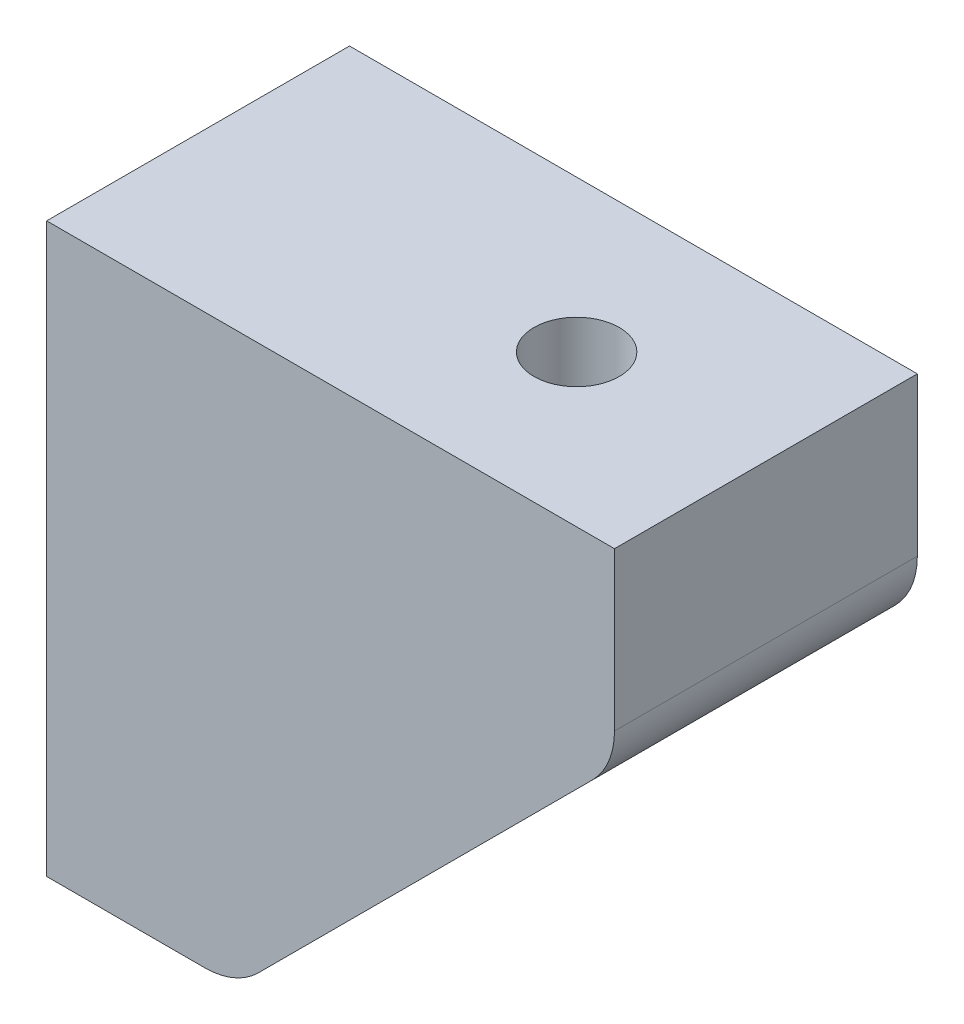
SolidWorks part; units mm, degrees
ref_plane "Front Plane" through (0, 0, 0) normal (0, 0, 1) x (1, 0, 0)
ref_plane "Top Plane" through (0, 0, 0) normal (0, 1, 0) x (1, 0, 0)
ref_plane "Right Plane" through (0, 0, 0) normal (1, 0, 0) x (0, 0, -1)
sketch "Sketch1" plane through (0, 0, 0) normal (0, 0, 1) x (1, 0, 0)
  line L0 (0, 0) -> (10, 0)
  line L1 (10, 0) -> (30, 20)
  line L2 (30, 20) -> (30, 30)
  line L3 (30, 30) -> (0, 30)
  line L4 (0, 30) -> (0, 0)
  line L5 (10, 0) -> (10, 30) construction
  line L6 (30, 20) -> (0, 20) construction
  dimension "D1" = 45
  dimension "D2" = 10
  dimension "D3" = 10
  dimension "D4" = 30
extrude "Boss-Extrude1" add sketch "Sketch1" along normal blind 16
sketch "Sketch2" plane through (0, 0, 0) normal (-1, 0, 0) x (0, 0, 1)
  line L0 (16, 20) -> (0, 20) construction
  line L1 (16, 20) -> (0, 20) construction
  line L3 (16, 0) -> (0, 0) construction
  line L5 (0, 20) -> (16, 0) construction
  circle A0 centre (8, 10) radius 2.5
  point P3 (0, 0)
  point P11 (22.7915, 10)
  point P12 (28, 0)
  dimension "D2" = 5
sketch "Sketch3" plane through (0, 30, 0) normal (0, 1, 0) x (1, 0, 0)
  line L0 (10, -16) -> (10, 0) construction
  line L1 (10, -16) -> (10, 0) construction
  line L5 (10, -16) -> (30, 0) construction
  circle A0 centre (20, -8) radius 2.25
  point P3 (0, 0)
  dimension "D2" = 4.5
extrude "Cut-Extrude1" cut sketch "Sketch3" against normal through all contours A0
extrude "Cut-Extrude2" cut sketch "Sketch2" against normal through all contours A0
ref_plane "Plane1" through (10, 0, 0) normal (-1, 0, 0) x (0, 0, 1)
sketch "Sketch4" plane through (10, 0, 0) normal (-1, 0, 0) x (0, 0, 1)
  circle A0 centre (8, 10) radius 2.5 construction
  circle A1 centre (8, 10) radius 2.5 construction
  circle A2 centre (8, 10) radius 5
  dimension "D1" = 10
extrude "Cut-Extrude3" cut sketch "Sketch4" against normal through all contours A2
ref_plane "Plane2" through (0, 20, 0) normal (0, 1, 0) x (1, 0, 0)
sketch "Sketch5" plane through (0, 20, 0) normal (0, 1, 0) x (1, 0, 0)
  circle A0 centre (20, -8) radius 2.25 construction
  circle A1 centre (20, -8) radius 2.25 construction
  circle A2 centre (20, -8) radius 4
  dimension "D1" = 8
extrude "Cut-Extrude4" cut sketch "Sketch5" against normal through all
chamfer "Chamfer1" distance 3 angle 45 1 edges at (10, 5, 8)
fillet "Fillet2" radius 4 2 edges at (10, 0, 8) (30, 20, 8)
